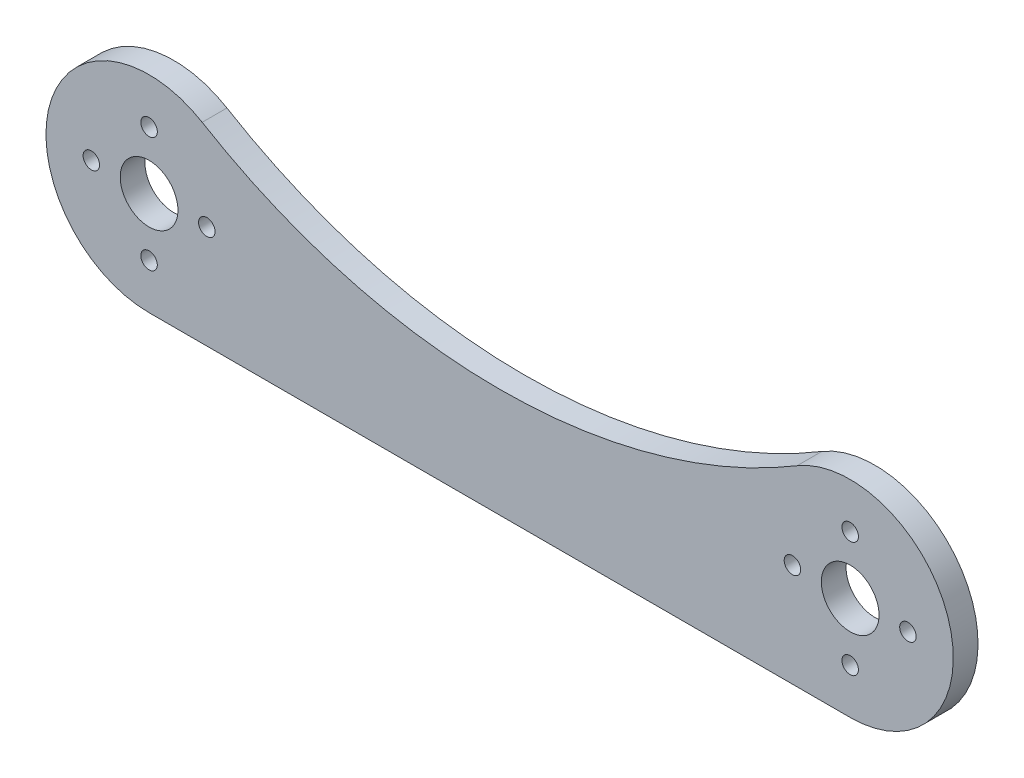
SolidWorks part; units mm, degrees
material "1345 Alloy"
ref_plane "Front Plane" through (0, 0, 0) normal (0, 0, 1) x (1, 0, 0)
ref_plane "Top Plane" through (0, 0, 0) normal (0, 1, 0) x (1, 0, 0)
ref_plane "Right Plane" through (0, 0, 0) normal (1, 0, 0) x (0, 0, -1)
sketch "Sketch1" plane through (0, 0, 0) normal (0, 0, 1) x (1, 0, 0)
  line L1 (-42.5, -12.5) -> (42.5, -12.5)
  circle A0 centre (-42.5, 0) radius 3.5
  circle A1 centre (42.5, 0) radius 3.5
  arc A2 (-36.0606, 10.7137) -> (-42.5, -12.5) centre (-42.5, 0) ccw
  arc A3 (42.5, -12.5) -> (36.0606, 10.7137) centre (42.5, 0) ccw
  arc A4 (-36.0606, 10.7137) -> (36.0606, 10.7137) centre (0, 70.7107) ccw
  circle A5 centre (-42.5, 7) radius 1
  circle A6 centre (-35.5, 0) radius 1
  circle A7 centre (-42.5, -7) radius 1
  circle A8 centre (-49.5, 0) radius 1
  circle A9 centre (42.5, 7) radius 1
  circle A10 centre (35.5, 0) radius 1
  circle A11 centre (42.5, -7) radius 1
  circle A12 centre (49.5, 0) radius 1
  point P5 (0, 0)
  dimension "D3" = 25
  dimension "D4" = 25
  dimension "D5" = 7
  dimension "D6" = 2
  dimension "D7" = 2
  dimension "D1" = 42.5
  dimension "D2" = 85
  dimension "D8" = 7
  dimension "D9" = 7
  dimension "D10" = 7
  dimension "D11" = 7
  dimension "D12" = 7
  dimension "D13" = 7
extrude "Boss-Extrude1" add sketch "Sketch1" along normal blind 3
ref_axis "Axis1" through (42.5, 0, 3) along (0, 0, -1)
ref_axis "Axis2" through (-42.5, 0, 3) along (0, 0, -1)
